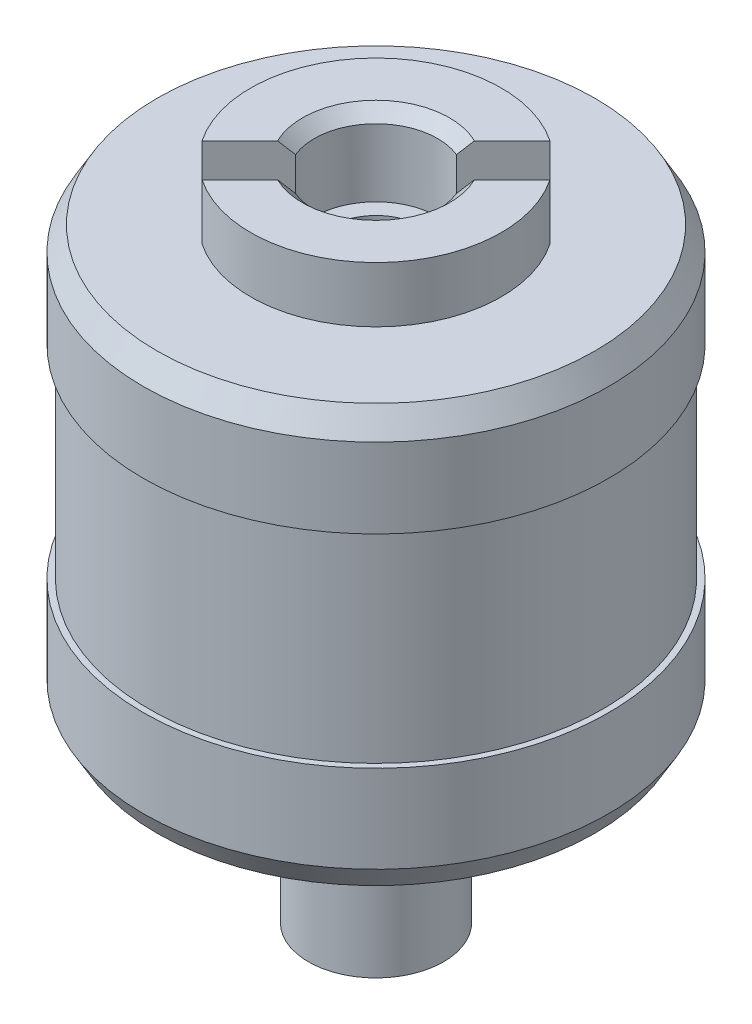
SolidWorks part; units mm, degrees
material "Хромированная нержавеющая сталь"
ref_plane "Front" through (0, 0, 0) normal (0, 0, 1) x (1, 0, 0)
ref_plane "Top" through (0, 0, 0) normal (0, 1, 0) x (1, 0, 0)
ref_plane "Right" through (0, 0, 0) normal (1, 0, 0) x (0, 0, -1)
sketch "Эскиз1" plane through (0, 0, 0) normal (1, 0, 0) x (0, 0, -1)
  line L0 (0, 0) -> (0, 17)
  line L1 (-5.5036, 15.6) -> (-3.15, 15.6)
  line L2 (-5.85, 15) -> (-5.85, 13)
  line L3 (-5.5036, 5.1) -> (-3.65, 5.1)
  line L4 (-3.65, 5.1) -> (-3.65, 4.6)
  line L5 (-3.65, 4.6) -> (-3.15, 4.6)
  line L6 (-1.25, 4) -> (-1.25, 3.0151)
  line L7 (-1.1287, 0) -> (0, 0)
  line L8 (-3.15, 15.6) -> (-3.15, 17)
  line L9 (-3.15, 17) -> (0, 17)
  line L10 (-5.85, 13) -> (-5.7, 13)
  line L11 (-5.7, 13) -> (-5.7, 7.9)
  line L12 (-5.7, 7.9) -> (-5.85, 7.9)
  line L13 (-5.85, 7.9) -> (-5.85, 5.7)
  line L14 (-5.85, 15) -> (-5.5036, 15.6)
  line L15 (-5.85, 5.7) -> (-5.5036, 5.1)
  line L16 (-3.15, 4) -> (-1.25, 4)
  line L17 (-3.15, 4.6) -> (-3.15, 4)
  line L18 (0, 0) -> (0, 20.0566) construction
  line L19 (-1.7, 0.4) -> (-1.1287, 0)
  line L20 (-1.25, 3.0151) -> (-1.7, 2.7)
  line L21 (-1.7, 2.7) -> (-1.7, 0.4)
  point P5 (-5.85, 5.1)
  point P10 (-5.85, 13)
  point P15 (-5.85, 7.9)
  dimension "D3" = 13
  dimension "D4" = 1.1
  dimension "D5" = 6.3
  dimension "D6" = 11.7
  dimension "D7" = 7.3
  dimension "D8" = 3.4
  dimension "D9" = 11.4
  dimension "D10" = 5.1
  dimension "D11" = 2.8
  dimension "D12" = 10.5
  dimension "D13" = 0.6
  dimension "D14" = 0.6
  dimension "D15" = 60
  dimension "D16" = 0.5
  dimension "D17" = 6.3
  dimension "D18" = 60
  dimension "D19" = 2.5
  dimension "D20" = 0.4
  dimension "D21" = 55
  dimension "D22" = 4
  dimension "D23" = 55
  dimension "D24" = 1.3
revolve "Повернуть1" add sketch "Эскиз1" angle 360 about L0
ref_axis "Ось1" through (0, 13, 0) along (0, 1, 0)
hole_wizard "#2-56 Tapped Hole1" positions "Трехмерный эскиз1" profile "Эскиз2" tap size "#2-56" standard "Ansi Inch"
sketch3d "Трехмерный эскиз1"
  point P0 (0, 10.6, -5.7)
  dimension "D1" = 5
sketch "Эскиз2" plane through (0, 10.6, -5.7) normal (1, 0, 0) x (0, 1, 0)
  line L0 (0, 0) -> (0, 4.2642)
  line L1 (0, 4.2642) -> (0.889, 3.73)
  line L2 (0.889, 3.73) -> (0.889, 0)
  line L5 (0.889, 0) -> (0, 0)
  line L10 (0, 4.2642) -> (-0.889, 3.73) construction
  line L11 (0, -6.35) -> (0, 107.95) construction
  dimension "Диаметр сверла" = 1.778
  dimension "Глубина сверла" = 3.73
  dimension "Угол заточки сверла" = 118
cosmetic thread "Отверстие резьбы1" parameters "D1"=3.37, "D2"=2.1844
hole_wizard "#4-40 Tapped Hole1" positions "Эскиз4" profile "Эскиз3" tap size "#4-40" standard "Ansi Inch"
sketch "Эскиз4" plane through (0, 17, 0) normal (0, 1, 0) x (-1, 0, 0)
  point P0 (0, 0)
sketch "Эскиз3" plane through (0, 17, 0) normal (1, 0, 0) x (0, 0, 1)
  line L0 (0, 0) -> (0, 8.2792)
  line L1 (0, 8.2792) -> (1.1303, 7.6)
  line L2 (1.1303, 7.6) -> (1.1303, 0)
  line L5 (1.1303, 0) -> (0, 0)
  line L10 (0, 8.2792) -> (-1.1303, 7.6) construction
  line L11 (0, -6.35) -> (0, 107.95) construction
  dimension "Диаметр сверла" = 2.2606
  dimension "Глубина сверла" = 7.6
  dimension "Угол заточки сверла" = 118
cosmetic thread "Отверстие резьбы2" parameters "D1"=5.69, "D2"=2.8448
sketch "Эскиз5" plane through (0, 17, 0) normal (0, 1, 0) x (-1, 0, 0)
  circle A0 centre (0, 0) radius 1.55
  dimension "D1" = 3.1
extrude "Вырез-Вытянуть1" cut sketch "Эскиз5" against normal blind 2
chamfer "Фаска1" distance 0.3 angle 45 1 edges at (0, 17, 1.55)
ref_plane "Плоскость1" through (0, 0, 0) normal (-0.7071, 0, 0.7071) x (0.7071, 0, 0.7071)
sketch "Эскиз6" plane through (0, 0, 0) normal (-0.7071, 0, 0.7071) x (0.7071, 0, 0.7071)
  line L0 (-0.6, 17) -> (-0.6, 15.6)
  line L1 (3.15, 17) -> (-3.15, 17) construction
  line L2 (-0.6, 15.6) -> (0.6, 15.6)
  line L3 (0.6, 15.6) -> (0.6, 17)
  line L4 (1.85, 17) -> (-1.85, 17) construction
  line L5 (0.6, 17) -> (-0.6, 17)
  dimension "D1" = 1.2
  dimension "D2" = 1.4
  dimension "D3" = 0.6
extrude "Вырез-Вытянуть2" cut sketch "Эскиз6" against normal up to next and the other way up to next
